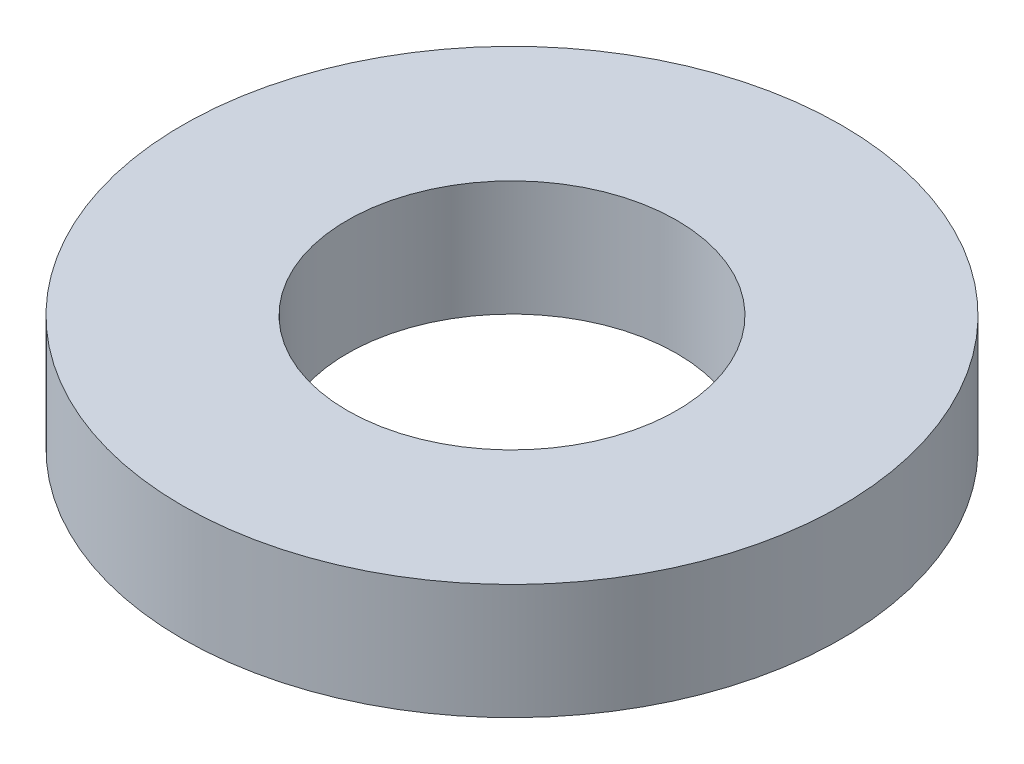
SolidWorks part; units mm, degrees
ref_plane "Front Plane" through (0, 0, 0) normal (0, 0, 1) x (1, 0, 0)
ref_plane "Top Plane" through (0, 0, 0) normal (0, 1, 0) x (1, 0, 0)
ref_plane "Right Plane" through (0, 0, 0) normal (1, 0, 0) x (0, 0, -1)
sketch "Sketch1" plane through (0, 0, 0) normal (0, 1, 0) x (1, 0, 0)
  circle A0 centre (0, 0) radius 80
  dimension "FLANGE_OD" = 160
extrude "Boss-Extrude1" add sketch "Sketch1" along normal blind 28
sketch "Sketch2" plane through (0, 0, 0) normal (0, 1, 0) x (1, 0, 0)
  circle A0 centre (0, 0) radius 40
  dimension "BORE_D" = 80
extrude "Cut-Extrude1" cut sketch "Sketch2" along normal through all
sketch "Sketch3" plane through (0, 28, 0) normal (0, 1, 0) x (1, 0, 0)
  circle A0 centre (0, 0) radius 22.0213 construction
  circle A1 centre (-22.0213, 0) radius 2.1493
  dimension "BOLT_D" = 4.2986
  dimension "BOLT_PCD" = 44.0426
extrude "Cut-Extrude2" cut sketch "Sketch3" against normal blind 18.3334 rebuild error yes
pattern_circular "CirPattern1" count 6 over 360 rebuild error yes
